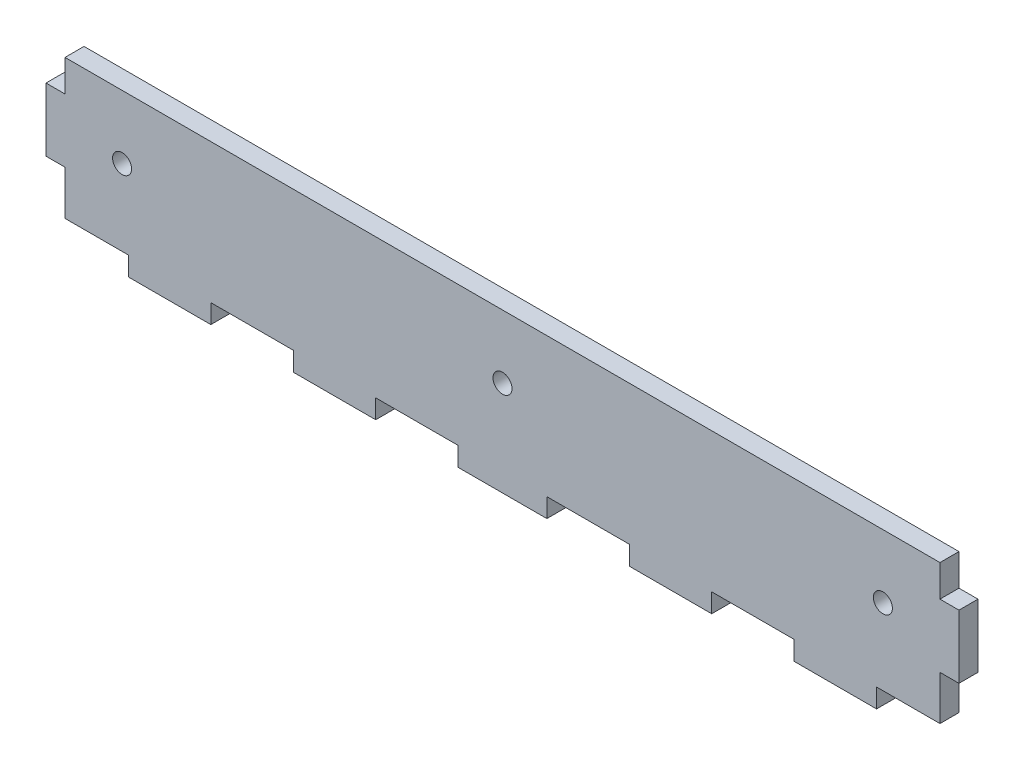
SolidWorks part; units mm, degrees
ref_plane "Front Plane" through (0, 0, 0) normal (0, 0, 1) x (1, 0, 0)
ref_plane "Top Plane" through (0, 0, 0) normal (0, 1, 0) x (1, 0, 0)
ref_plane "Right Plane" through (0, 0, 0) normal (1, 0, 0) x (0, 0, -1)
sketch "Sketch1" plane through (0, 0, 0) normal (0, 0, 1) x (1, 0, 0)
  line L0 (0, 17) -> (0, 22)
  line L1 (0, 0) -> (10, 0)
  line L2 (0, 0) -> (0, 7)
  line L3 (0, 22) -> (138, 22)
  line L4 (138, 0) -> (138, 7)
  line L5 (0, 17) -> (-3, 17)
  line L6 (138, 17) -> (138, 22)
  line L7 (0, 7) -> (-3, 7)
  line L8 (-3, 17) -> (-3, 7)
  line L9 (138, 17) -> (141, 17)
  line L10 (23, 0) -> (36, 0)
  line L11 (138, 7) -> (141, 7)
  line L12 (141, 17) -> (141, 7)
  line L14 (10, 0) -> (10, -3)
  line L15 (10, -3) -> (23, -3)
  line L16 (23, 0) -> (23, -3)
  line L18 (36, 0) -> (36, -3)
  line L19 (36, -3) -> (49, -3)
  line L20 (49, 0) -> (49, -3)
  line L22 (62, 0) -> (62, -3)
  line L23 (62, -3) -> (76, -3)
  line L24 (76, 0) -> (76, -3)
  line L26 (89, 0) -> (89, -3)
  line L27 (89, -3) -> (102, -3)
  line L28 (102, 0) -> (102, -3)
  line L30 (115, 0) -> (115, -3)
  line L31 (115, -3) -> (128, -3)
  line L32 (128, 0) -> (128, -3)
  line L33 (49, 0) -> (62, 0)
  line L34 (76, 0) -> (89, 0)
  line L35 (102, 0) -> (115, 0)
  line L36 (128, 0) -> (138, 0)
  circle A0 centre (9, 12) radius 1.5
  circle A1 centre (69, 12) radius 1.5
  circle A2 centre (129, 12) radius 1.5
  dimension "D17" = 3
  dimension "D18" = 3
  dimension "D19" = 3
  dimension "D1" = 138
  dimension "D2" = 22
  dimension "D3" = 5
  dimension "D4" = 7
  dimension "D5" = 3
  dimension "D6" = 14
  dimension "D7" = 10
  dimension "D8" = 10
  dimension "D9" = 13
  dimension "D10" = 13
  dimension "D11" = 13
  dimension "D12" = 13
  dimension "D13" = 13
  dimension "D14" = 13
  dimension "D15" = 13
  dimension "D16" = 3
  dimension "D20" = 9
  dimension "D21" = 9
  dimension "D22" = 60
  dimension "D23" = 10
extrude "Boss-Extrude1" add sketch "Sketch1" along normal blind 3
